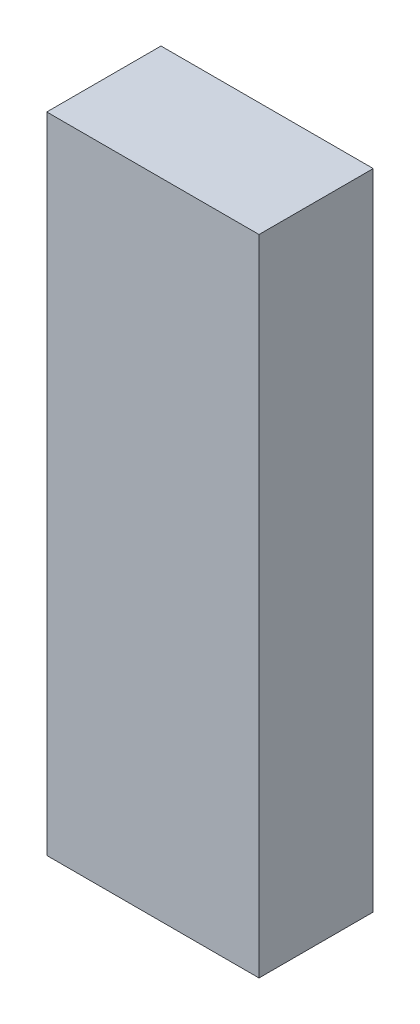
SolidWorks part; units mm, degrees
ref_plane "Front Plane" through (0, 0, 0) normal (0, 0, 1) x (1, 0, 0)
ref_plane "Top Plane" through (0, 0, 0) normal (0, 1, 0) x (1, 0, 0)
ref_plane "Right Plane" through (0, 0, 0) normal (1, 0, 0) x (0, 0, -1)
sketch "Sketch1" plane through (0, 0, 0) normal (0, 1, 0) x (1, 0, 0)
  line L0 (-6.8601, 1.3924) -> (-8.8675, 1.3924)
  line L1 (-8.8675, 1.3924) -> (-8.8675, -8.1513)
  line L2 (-8.8675, -8.1513) -> (8.8675, -8.1513)
  line L3 (0, 0) -> (0, 18.1102) construction
  line L4 (6.8601, 1.3924) -> (8.8675, 1.3924)
  line L5 (8.8675, 1.3924) -> (8.8675, -8.1513)
  arc A0 (-6.8601, 1.3924) -> (6.8601, 1.3924) centre (0, 0) ccw
  point P9 (0, -8.1513)
  dimension "D1" = 14
extrude "Boss-Extrude1" add sketch "Sketch1" along normal blind 51
sketch "Sketch2" plane through (0, 0, 0) normal (0, -1, 0) x (1, 0, 0)
  line L1 (-8.8675, -1.3924) -> (8.8675, -1.3924)
  line L2 (-8.8675, -1.3924) -> (-8.8675, 8.1513)
  line L3 (-8.8675, 8.1513) -> (8.8675, 8.1513)
  line L4 (8.8675, -1.3924) -> (8.8675, 8.1513)
extrude "Boss-Extrude2" add sketch "Sketch2" along normal blind 1.4
extrude "Boss-Extrude3" add sketch "Sketch2<2>" against normal blind 1.4 from surface starting at face at (0, 51, 3.1876)
sketch "Sketch2<2>" plane through (0, 0, 0) normal (0, -1, 0) x (1, 0, 0) same geometry as "Sketch2"
